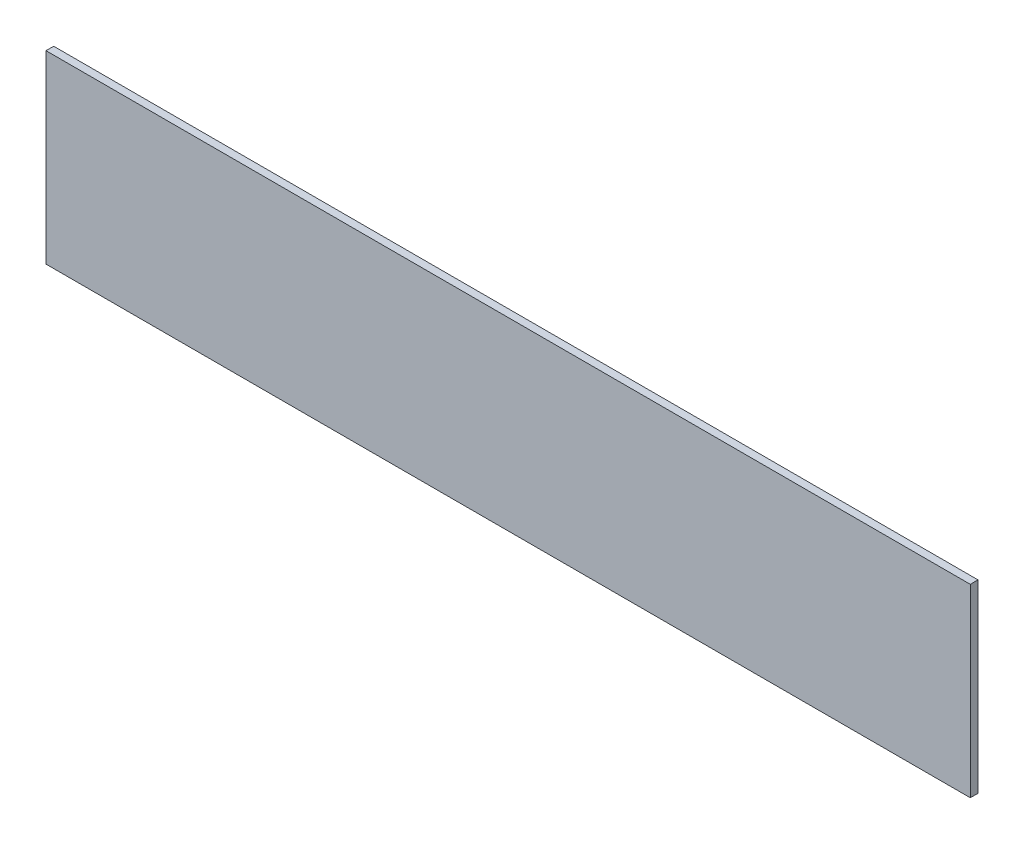
SolidWorks part; units mm, degrees
material "A-Glass Fiber"
ref_plane "Front Plane" through (0, 0, 0) normal (0, 0, 1) x (1, 0, 0)
ref_plane "Top Plane" through (0, 0, 0) normal (0, 1, 0) x (1, 0, 0)
ref_plane "Right Plane" through (0, 0, 0) normal (1, 0, 0) x (0, 0, -1)
sketch "Sketch1" plane through (0, 0, 0) normal (0, 0, 1) x (1, 0, 0)
  line L1 (0, 0) -> (190.5, 0)
  line L2 (0, 0) -> (0, 38.1)
  line L3 (0, 38.1) -> (190.5, 38.1)
  line L4 (190.5, 0) -> (190.5, 38.1)
  dimension "D1" = 190.5
  dimension "D2" = 38.1
extrude "Boss-Extrude1" add sketch "Sketch1" along normal blind 1.5875
